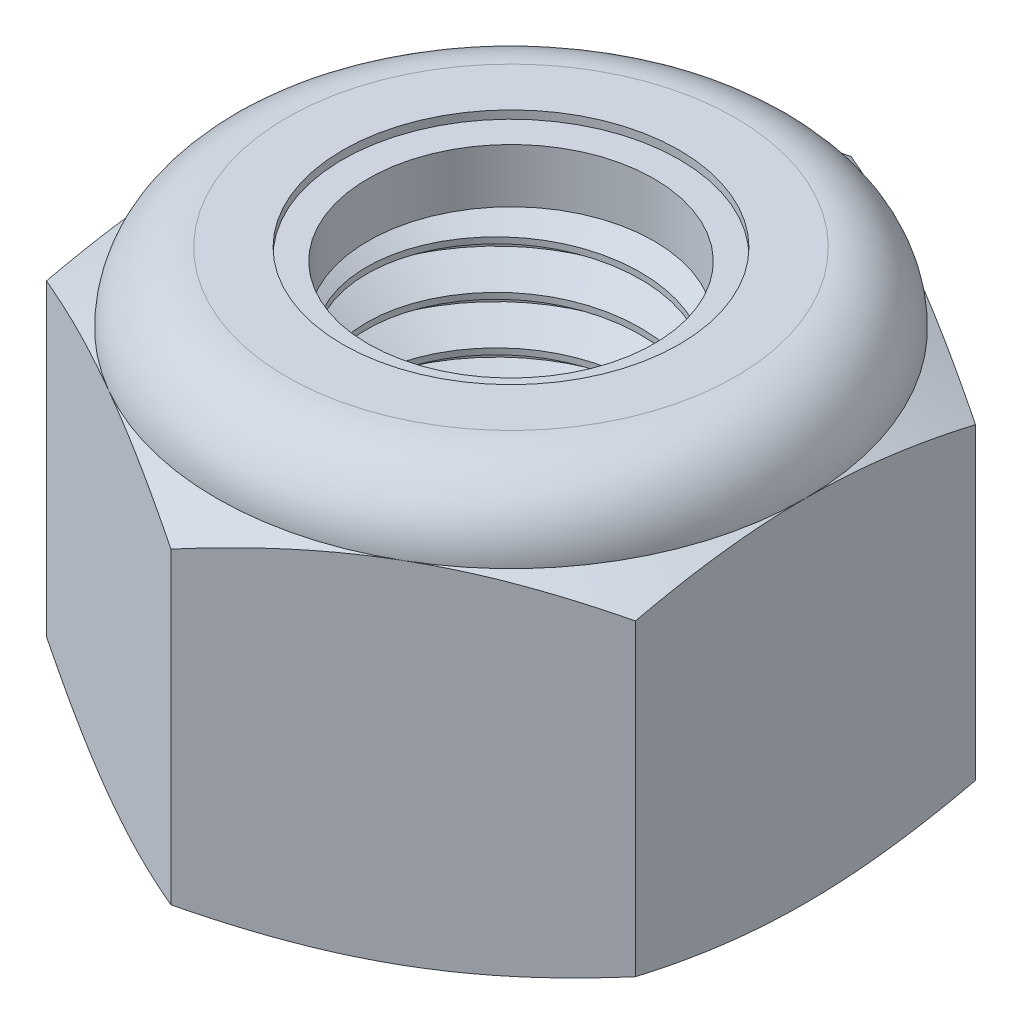
SolidWorks part; units mm, degrees
note: '?' marks a value the reader was unsure of.
ref_plane "Front" through (0, 0, 0) normal (0, 0, 1) x (1, 0, 0)
ref_plane "Top" through (0, 0, 0) normal (0, 1, 0) x (1, 0, 0)
ref_plane "Right" through (0, 0, 0) normal (1, 0, 0) x (0, 0, -1)
sketch "Sketch8" plane through (0, 0, 0) normal (1, 0, 0) x (0, 0, -1)
  line L0 (0, 0) -> (0, 7.9375) construction
  line L1 (5.5562, 0) -> (-5.5562, 0) construction
  line L2 (-3.175, 7.9375) -> (3.175, 7.9375) construction
  line L3 (3.175, 7.9375) -> (3.175, 7.0304) construction
sketch "Sketch1" plane through (0, 0, 0) normal (0, 1, 0) x (1, 0, 0)
  line L1 (0, 6.4158) -> (-5.5563, 3.2079)
  line L2 (-5.5563, 3.2079) -> (-5.5563, -3.2079)
  line L3 (-5.5563, -3.2079) -> (0, -6.4158)
  line L4 (0, -6.4158) -> (5.5563, -3.2079)
  line L5 (5.5563, -3.2079) -> (5.5563, 3.2079)
  line L6 (5.5563, 3.2079) -> (0, 6.4158)
  circle A0 centre (0, 0) radius 5.5562 construction
  circle A1 centre (0, 0) radius 3.175
extrude "Extrude1" add sketch "Sketch1" along normal up to vertex (7.9375 mm away) up to point (0, 7.9375, 0)
sketch "Sketch5" plane through (0, 0, 0) normal (1, 0, 0) x (0, 0, -1)
  line L0 (0, 0) -> (5.5562, 0)
  line L1 (5.5562, 0) -> (6.4158, 0.4008)
  line L2 (6.4158, 0.4008) -> (6.4158, 6.2138)
  line L3 (6.4158, 6.2138) -> (5.5562, 6.6146)
  line L4 (4.2333, 7.9375) -> (4.2333, 9.2075)
  line L5 (4.2333, 9.2075) -> (7.6858, 9.2075)
  line L6 (7.6858, 9.2075) -> (7.6858, -1.27)
  line L7 (7.6858, -1.27) -> (0, -1.27)
  line L8 (0, -1.27) -> (0, 0)
  line L9 (5.5562, 6.6146) -> (5.5562, 0) construction
  line L12 (6.4158, 7.9375) -> (6.4158, 0) construction
  line L13 (6.4158, 3.9688) -> (7.6858, 3.9688) construction
  line L15 (0, 0) -> (0, 9.2075) construction
  line L18 (5.5562, 0) -> (-5.5562, 0) construction
  line L19 (3.2079, 7.9375) -> (6.4158, 7.9375) construction
  line L20 (0, 9.2075) -> (4.2333, 9.2075) construction
  line L21 (3.2079, 0) -> (6.4158, 0) construction
  arc A0 (5.5562, 6.6146) -> (4.2333, 7.9375) centre (4.2333, 6.6146) ccw
  dimension "D1" = 25
  dimension "D2" = 1.27
  dimension "D4" = 1.3229
revolve "Cut-Revolve3" cut sketch "Sketch5" angle 360 about L15
sketch "Sketch4" plane through (0, 0, 0) normal (1, 0, 0) x (0, 0, -1)
  line L0 (0, 6.6146) -> (3.4925, 6.6146)
  line L1 (3.4925, 6.6146) -> (0, 4.986)
  line L3 (0, 1.6286) -> (3.4925, 0)
  line L4 (3.4925, 0) -> (0, 0)
  line L5 (0, 0) -> (0, 6.6146) construction
  line L10 (0, 0) -> (0, 7.9375) construction
  line L11 (0, 1.6286) -> (0, 0)
  line L12 (0, 6.6146) -> (0, 4.986)
  line L13 (4.8119, 6.6146) -> (0, 6.6146) construction
  dimension "D1" = 25
  dimension "D2" = 6.985
sketch "Sketch6" plane through (0, 0, 0) normal (1, 0, 0) x (0, 0, -1)
  line L0 (0, 6.6146) -> (5.4038, 6.6146)
  line L1 (4.2333, 7.7851) -> (2.1167, 7.7851)
  line L2 (0, 9.2075) -> (0, 6.6146)
  line L3 (2.1167, 9.2075) -> (0, 9.2075)
  line L4 (0, 9.2075) -> (4.2333, 9.2075) construction
  line L5 (0, 0) -> (0, 9.2075) construction
  line L6 (0, 9.2075) -> (0, 0) construction
  line L7 (2.1167, 7.7851) -> (2.1167, 9.2075)
  line L8 (4.2333, 7.9375) -> (4.2333, 7.7851) construction
  line L9 (2.1167, 7.7851) -> (0, 7.7851) construction
  line L10 (0, 7.7851) -> (0, 4.986) construction
  arc A0 (5.4038, 6.6146) -> (4.2333, 7.7851) centre (4.2333, 6.6146) ccw
  arc A1 (5.5562, 6.6146) -> (4.2333, 7.9375) centre (4.2333, 6.6146) ccw construction
  dimension "D1" = 0.1524
revolve "Cut-Revolve4" cut sketch "Sketch6" angle 360 about L6
revolve "Cut-Revolve2" cut sketch "Sketch4" angle 360 about L5
sketch "Sketch7" plane through (0, 0, 0) normal (1, 0, 0) x (0, 0, -1)
  line L0 (2.6988, 6.6908) -> (5.325, 6.6908)
  line L1 (4.2333, 7.7089) -> (2.6988, 7.7089)
  line L2 (2.6988, 7.7089) -> (2.6988, 6.6908)
  line L3 (2.6988, 6.6908) -> (0, 6.6908) construction
  line L4 (0, 6.6908) -> (0, 7.7089) construction
  line L5 (0, 7.7089) -> (2.6988, 7.7089) construction
  line L6 (2.6988, 6.6908) -> (2.6988, 6.6146) construction
  line L7 (0, 6.6146) -> (5.4038, 6.6146) construction
  line L8 (4.2333, 7.7089) -> (4.2333, 7.7851) construction
  arc A0 (5.325, 6.6908) -> (4.2333, 7.7089) centre (4.2333, 6.6146) ccw
  arc A2 (5.4038, 6.6146) -> (4.2333, 7.7851) centre (4.2333, 6.6146) ccw construction
  dimension "D1" = 0.0762
  dimension "D2" = 5.3975
revolve "Revolve2" add sketch "Sketch7" angle 360 about L4
sketch "Sketch2" plane through (0, 0, 0) normal (1, 0, 0) x (0, 0, -1)
  line L0 (-3.175, 0) -> (-3.175, 6.6146) construction
  line L1 (0, 0) -> (3.175, 0)
  line L2 (0, 0) -> (0, 6.6146)
  line L3 (0, 6.6146) -> (3.175, 6.6146)
  line L4 (3.175, 0) -> (3.175, 6.6146)
  line L6 (4.8119, 6.6146) -> (5.5562, 6.6146) construction
  line L7 (0, -3.175) -> (0, 0) construction
revolve "Revolve1" add sketch "Sketch2" angle 360 about L7
sketch "Sketch9" plane through (0, 0, 0) normal (1, 0, 0) x (0, 0, -1)
  line L0 (3.2732, 7.465) -> (3.2732, 6.5579) construction
  line L1 (3.2732, 6.5579) -> (2.4876, 7.0115) construction
  line L2 (2.4876, 7.0115) -> (3.2732, 7.465) construction
  line L3 (2.5858, 7.0682) -> (2.5858, 6.9548) construction
  line L4 (3.175, 7.4083) -> (3.175, 6.6146) construction
  line L5 (2.4876, 7.0115) -> (2.5858, 7.0115) construction
  line L6 (3.175, 7.0115) -> (3.2732, 7.0115) construction
  line L7 (3.2241, 7.0115) -> (3.2241, 7.4367) construction
  line L8 (3.2732, 6.5579) -> (3.2241, 7.4367)
  line L9 (3.2241, 7.4367) -> (2.5858, 7.0682)
  line L10 (2.5858, 7.0682) -> (2.5858, 6.9548)
  line L11 (2.5858, 6.9548) -> (3.2732, 6.5579)
  dimension "D1" = 0.9071
  dimension "D2" = 0.1134
sketch "Sketch10" plane through (0, 6.6146, 0) normal (0, 1, 0) x (1, 0, 0)
  circle A1 centre (0, 0) radius 3.175
  circle A2 centre (0, 0) radius 3.175
  dimension "D1" = 0
curve "Helix/Spiral1" pitch 0.9071 height 8.8446 turns 9.75
sweep "Cut-Sweep1" cut profiles "Sketch9" path "Helix/Spiral1" align with end faces yes
sketch "Sketch11" plane through (0, 0, 0) normal (1, 0, 0) x (0, 0, -1)
  line L0 (0, 0) -> (0, 7.9375) construction
  line L1 (5.5562, 0) -> (-5.5562, 0) construction
  line L4 (0, 7.9375) -> (0, 0) construction
  line L5 (0, 3.9688) -> (3.175, 3.9688) construction
  line L6 (0, 0) -> (3.4925, 0)
  line L7 (0, 1.6286) -> (0, 0)
  line L8 (3.4925, 0) -> (0, 1.6286)
  dimension "D1" = 6.985
  dimension "D2" = 25
revolve "Revolve3" add sketch "Sketch11" angle 360 about L4
sketch "Sketch12" plane through (0, 0, 0) normal (1, 0, 0) x (0, 0, -1)
  line L0 (3.4925, 6.6146) -> (0, 6.6146)
  line L1 (0, 6.6146) -> (0, 0)
  line L2 (0, 0) -> (3.4925, 0)
  line L3 (5.5562, 0) -> (-5.5562, 0) construction
  line L4 (3.4925, 0) -> (3.4925, 6.6146)
  line L5 (-3.4925, 0) -> (3.4925, 0) construction
revolve "Revolve4" add sketch "Sketch12" angle 360 about L0
combine bodies "Combine1" operation type subtract main body 136 bodies to subtract 133
ref_plane "Contact Plane 1" through (0, 0, 0) normal (0, -1, 0) x (1, 0, 0)
ref_axis "Center Axis 1" through (0, -2.1015, 0) along (0, 1, 0)?
equation "\"D4@Sketch5\"=\"Height@Sketch8\"/6"
equation "\"D1@Sketch9\"=\"Thread Pitch@Sketch8\""
equation "\"D2@Sketch9\"=\"Thread Pitch@Sketch8\"/8"
equation "\"D4@Helix/Spiral1\"=\"Thread Pitch@Sketch8\""
equation "\"D3@Helix/Spiral1\"=\"Thread Pitch@Sketch8\"+\"Height@Sketch8\""
equation "\"D2@Sketch4\"=\"Thread Dia@Sketch8\"*1.1"
equation "\"D1@Sketch11\"=\"Thread Dia@Sketch8\"*1.1"
equation "\"D2@Sketch7\"=\"Thread Dia@Sketch8\"*.85"
